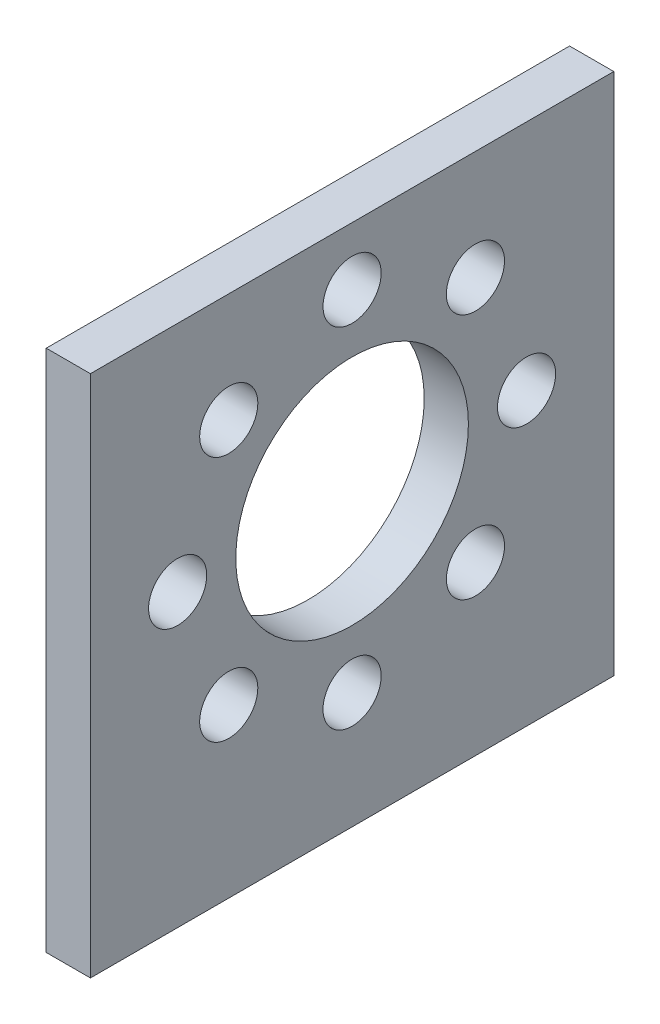
SolidWorks part; units mm, degrees
ref_plane "Front Plane" through (0, 0, 0) normal (0, 0, 1) x (1, 0, 0)
ref_plane "Top Plane" through (0, 0, 0) normal (0, 1, 0) x (1, 0, 0)
ref_plane "Right Plane" through (0, 0, 0) normal (1, 0, 0) x (0, 0, -1)
sketch "Sketch2" plane through (0, 0, 0) normal (1, 0, 0) x (0, 0, -1)
  line L0 (-48.0119, 35.4849) -> (-48.0119, -21.6651)
  line L1 (-48.0119, -21.6651) -> (9.1381, -21.6651)
  line L2 (9.1381, -21.6651) -> (9.1381, 35.4849)
  line L3 (9.1381, 35.4849) -> (-48.0119, 35.4849)
  line L4 (-19.4369, 35.4849) -> (-19.4369, -21.6651) construction
  line L5 (-48.0119, 35.4849) -> (9.1381, -21.6651) construction
  line L6 (9.1381, 35.4849) -> (-48.0119, -21.6651) construction
  circle A0 centre (-19.4369, 10.0849) radius 12.7
  circle A1 centre (-19.4369, 10.0849) radius 25.4
  circle A2 centre (-19.4369, 29.1349) radius 3.175
  dimension "D2" = 25.4
  dimension "D3" = 25.4
  dimension "D4" = 50.8
  dimension "D5" = 19.05
  dimension "D6" = 6.35
  dimension "D1" = 57.15
extrude "Boss-Extrude2" add sketch "Sketch2" along normal blind 4.826 contours A2 | A1 A2 A0 | L3 A1 L0 L1 L2 region at (0, 27.5374, 1.9844) region at (0, 34.6767, 33.7244) region at (0, 29.1349, 19.4369)
extrude "Cut-Extrude4" cut sketch "Sketch2<4>" along normal through all contours A2 region at (0, 29.1349, 19.4369)
sketch "Sketch2<4>" plane through (0, 0, 0) normal (1, 0, 0) x (0, 0, -1) same geometry as "Sketch2"
sketch "Sketch4" plane through (0, 0, 0) normal (1, 0, 0) x (0, 0, -1)
  line L0 (-19.4369, 10.0849) -> (-19.4369, 21.3784) construction
pattern_circular "CirPattern1" count 8 over 360 about axis through (4.826, 10.0849, 19.4369) along (-1, 0, 0) of "Cut-Extrude4"
